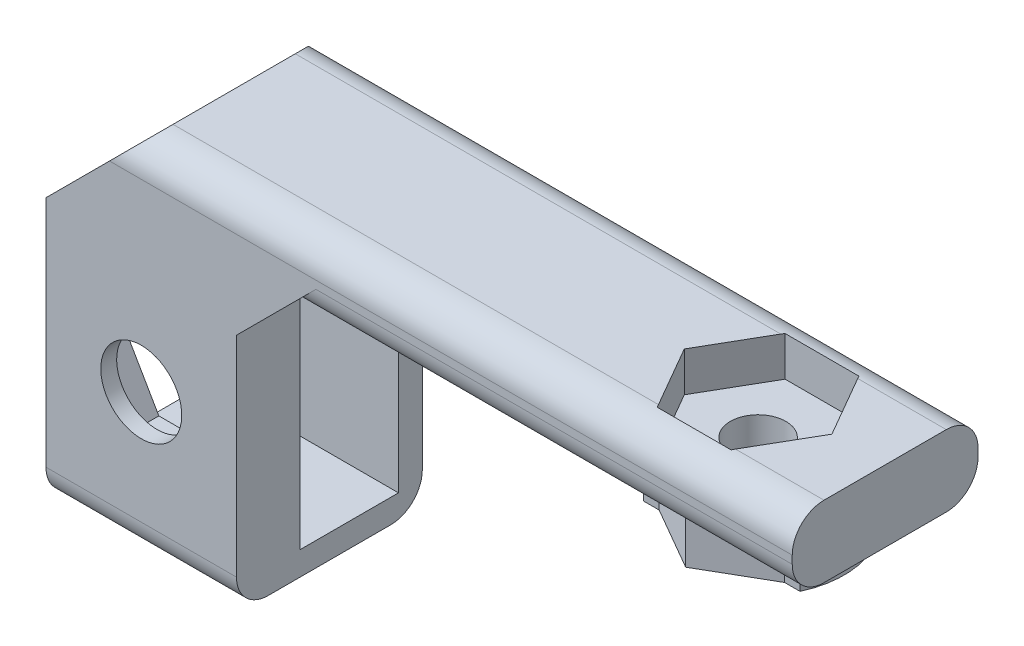
SolidWorks part; units mm, degrees
note: The reader was unsure of these and kept them because the rebuilt part matched: shared geometry of "Sketch2<4>", "Sketch5<2>".
ref_plane "Front Plane" through (0, 0, 0) normal (0, 0, 1) x (1, 0, 0)
ref_plane "Top Plane" through (0, 0, 0) normal (0, 1, 0) x (1, 0, 0)
ref_plane "Right Plane" through (0, 0, 0) normal (1, 0, 0) x (0, 0, -1)
sketch "Sketch1" plane through (0, 0, 0) normal (0, 1, 0) x (1, 0, 0)
  line L0 (-3.95, 2.2805) -> (-4.9224, 2.2805)
  line L1 (0, 4.5611) -> (-3.95, 2.2805)
  line L3 (-3.95, -2.2805) -> (0, -4.5611)
  line L4 (0, -4.5611) -> (3.95, -2.2805)
  line L6 (3.95, 2.2805) -> (0, 4.5611)
  line L7 (-3.95, -2.2805) -> (-4.9224, -2.2805)
  line L8 (3.95, 2.2805) -> (4.9224, 2.2805)
  line L9 (3.95, -2.2805) -> (4.9224, -2.2805)
  line L11 (-3.95, 0) -> (-3.95, -2.2805) [skipped]
  line L12 (3.95, -2.2805) -> (3.95, 0) [skipped]
  circle A0 centre (0, 0) radius 3.95 construction
  arc A1 (-4.9224, 2.2805) -> (-4.9224, -2.2805) centre (0, 0) ccw
  circle A2 centre (0, 0) radius 1.75
  arc A3 (4.9224, -2.2805) -> (4.9224, 2.2805) centre (0, 0) ccw
  dimension "D1" = 7.9
  dimension "D2" = 3.5
  dimension "D3" = 10.85
extrude "Boss-Extrude1" add sketch "Sketch1" along normal blind 2.8
sketch "Sketch2" plane through (0, 2.8, 0) normal (0, 1, 0) x (1, 0, 0)
  line L1 (8, 5.85) -> (-39, 5.85)
  line L2 (8, 5.85) -> (8, -5.85)
  line L3 (8, -5.85) -> (-39, -5.85)
  line L4 (-39, 5.85) -> (-39, -5.85)
  line L11 (4.6477, 0) -> (2.3238, 4.025)
  line L12 (2.3238, 4.025) -> (-2.3238, 4.025)
  line L13 (-2.3238, 4.025) -> (-4.6477, 0)
  line L14 (-4.6477, 0) -> (-2.3238, -4.025)
  line L15 (-2.3238, -4.025) -> (2.3238, -4.025)
  line L16 (2.3238, -4.025) -> (4.6477, 0)
  circle A1 centre (0, 0) radius 4.025 construction
  line M12 (3.95, 2.2805) -> (0, 4.5611)
  line M13 (0, 4.5611) -> (-3.95, 2.2805)
  line M14 (-3.95, 2.2805) -> (-4.9224, 2.2805)
  arc M15 (-4.9224, 2.2805) -> (-4.9224, -2.2805) centre (0, 0) ccw
  line M16 (-4.9224, -2.2805) -> (-3.95, -2.2805)
  line M17 (-3.95, -2.2805) -> (0, -4.5611)
  line M18 (0, -4.5611) -> (3.95, -2.2805)
  line M19 (3.95, -2.2805) -> (4.9224, -2.2805)
  arc M20 (4.9224, -2.2805) -> (4.9224, 2.2805) centre (0, 0) ccw
  line M21 (4.9224, 2.2805) -> (3.95, 2.2805)
  circle M22 centre (0, 0) radius 1.75
  dimension "D1" = 8.05
  dimension "D2" = 11.7
extrude "Boss-Extrude2" add sketch "Sketch2" along normal blind 4.5 contours L1 L4 L3 L2 L16 L15 L14 L13 L12 L11 M18 M17 M16 M15 M14 M13 M12 M21 M20 M19 | L14 L13 M13 M14 M15 M16 M17 | L16 L11 M18 M19 M20 M21 M12 | L15 M17 M18 | L12 M12 M13
extrude "Boss-Extrude3" add sketch "Sketch2<4>" along normal blind 2 contours L11 L12 M12 | L16 L11 L12 L13 L14 L15 M18 M12 M13 M17 M22 | L15 L16 M18 | L14 L15 M17 | L12 L13 M13
sketch "Sketch2<4>" plane through (0, 2.8, 0) normal (0, 1, 0) x (1, 0, 0) same geometry as "Sketch2"
sketch "Sketch3" plane through (0, 2.8, 0) normal (0, -1, 0) x (1, 0, 0)
  line L0 (8, 5.85) -> (-39, 5.85) construction
  line L1 (-39, -5.85) -> (-27, -5.85)
  line L2 (-39, -5.85) -> (-39, 5.85)
  line L3 (-39, 5.85) -> (-27, 5.85)
  line L4 (-27, -5.85) -> (-27, 5.85)
  dimension "D1" = 12
extrude "Boss-Extrude4" add sketch "Sketch3" along normal blind 18.2
sketch "Sketch4" plane through (-39, 0, 0) normal (-1, 0, 0) x (0, 0, 1)
  line L0 (-4.35, -6.3) -> (-5.85, -6.3) construction
  line L1 (1.85, 1.3) -> (-4.35, 1.3)
  line L2 (1.85, 1.3) -> (1.85, -13.9)
  line L3 (1.85, -13.9) -> (-4.35, -13.9)
  line L4 (-4.35, 1.3) -> (-4.35, -13.9)
  line L5 (1.85, 1.3) -> (-4.35, -13.9) construction
  line L6 (1.85, -13.9) -> (-4.35, 1.3) construction
  line L7 (-5.85, 7.3) -> (-5.85, -15.4) construction
  line L8 (-1.25, -13.9) -> (-1.25, -15.4) construction
  line L9 (5.85, -15.4) -> (-5.85, -15.4) construction
  line L12 (1.85, -6.3) -> (5.85, -6.3) construction
  line L13 (5.85, 7.3) -> (5.85, -15.4) construction
  point P0 (-1.25, -6.3)
  dimension "D1" = 4
  dimension "D2" = 6.2
  dimension "D3" = 15.2
  dimension "D4" = 15.2
extrude "Cut-Extrude2" cut sketch "Sketch4" against normal blind 17.2
sketch "Sketch5" plane through (0, 0, 1.85) normal (0, 0, -1) x (-1, 0, 0)
  line L0 (39, -6.3) -> (27, -6.3) construction
  line L8 (38.635, -6.3) -> (35.8926, -1.55)
  line L9 (39, -13.9) -> (39, 1.3) construction
  line L10 (27, -13.9) -> (27, 1.3) construction
  line L11 (27, 1.3) -> (39, 1.3) construction
  line L12 (35.8926, -1.55) -> (30.4077, -1.55)
  line L13 (30.4077, -1.55) -> (27.6653, -6.3)
  line L14 (27.6653, -6.3) -> (30.4077, -11.05)
  line L15 (30.4077, -11.05) -> (35.8926, -11.05)
  line L16 (35.8926, -11.05) -> (38.635, -6.3)
  circle A0 centre (33.1501, -6.3) radius 4.75 construction
  circle A1 centre (33, -6.3) radius 2.55
  point P19 (33, -6.3)
  dimension "D1" = 9.5
  dimension "D2" = 5.1
extrude "Cut-Extrude4" cut sketch "Sketch5" against normal blind 3
extrude "Cut-Extrude5" cut sketch "Sketch5<2>" against normal through all contours A1
sketch "Sketch5<2>" plane through (0, 0, 1.85) normal (0, 0, -1) x (-1, 0, 0) same geometry as "Sketch5"
fillet "Fillet1" radius 2 4 edges at (-33, -15.4, 5.85) (-15.5, 7.3, 5.85) (-15.5, 7.3, -5.85) (-33, -15.4, -5.85)
chamfer "Chamfer1" distance 3 angle 45 1 edges at (-27, 2.8, 0)
fillet "Fillet2" radius 2 2 edges at (-8, 2.8, 5.85) (-8, 2.8, -5.85)
chamfer "Chamfer2" distance 6 angle 45 3 edges at (-39, 7.3, 0) (-39, 6.7142, -5.2642) (-39, 6.7142, 5.2642)
